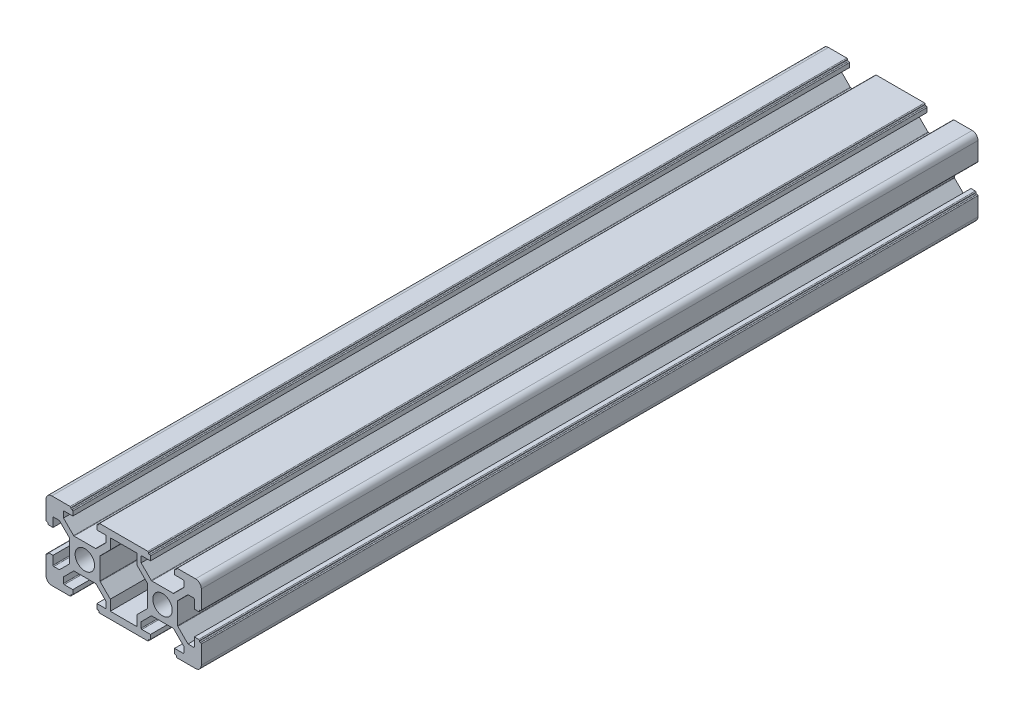
SolidWorks part; units mm, degrees
ref_plane "前视基准面" through (0, 0, 0) normal (0, 0, 1) x (1, 0, 0)
ref_plane "上视基准面" through (0, 0, 0) normal (0, 1, 0) x (1, 0, 0)
ref_plane "右视基准面" through (0, 0, 0) normal (1, 0, 0) x (0, 0, -1)
sketch "Sketch1" plane through (0, 0, 0) normal (0, 0, 1) x (1, 0, 0)
  line L0 (-8.5, 10) -> (-3.8, 10)
  line L3 (-8.5, -10) -> (-3.8, -10)
  line L5 (-10, 8.5) -> (-10, 3.8)
  line L6 (-2.7565, 3.9) -> (2.7565, 3.9)
  line L9 (-2.7565, -3.9) -> (2.7565, -3.9)
  line L10 (3.9, 2.7565) -> (3.9, -2.7565)
  line L11 (-3.9, 2.7565) -> (-3.9, -2.7565)
  line L12 (-3.9586, -2.8979) -> (-6.5607, -5.5)
  line L13 (3.6, 9.7) -> (3.6, 9.8)
  line L14 (3.1, -8.2) -> (5.3, -8.2)
  line L15 (-2.8979, -3.9586) -> (-5.5, -6.5607)
  line L16 (-3.1, -8.2) -> (-3.1, -9.3)
  line L17 (3.1, -8.2) -> (3.1, -9.3)
  line L18 (-5.5, -6.5607) -> (-5.5, -8)
  line L19 (5.5, -6.5607) -> (5.5, -8)
  line L20 (-5.3, -8.2) -> (-3.1, -8.2)
  line L21 (-3.4, -9.5) -> (-3.3, -9.5)
  line L22 (3.8, -10) -> (8.5, -10)
  line L23 (3.3, -9.5) -> (3.4, -9.5)
  line L24 (-3.6, -9.7) -> (-3.6, -9.8)
  line L25 (3.6, -9.7) -> (3.6, -9.8)
  line L26 (-6.5607, -5.5) -> (-8, -5.5)
  line L27 (-9.7, -3.6) -> (-9.8, -3.6)
  line L28 (-9.5, -3.4) -> (-9.5, -3.3)
  line L29 (-8.2, -3.1) -> (-9.3, -3.1)
  line L30 (-8.2, -5.3) -> (-8.2, -3.1)
  line L31 (-10, -3.8) -> (-10, -8.5)
  line L33 (3.8, 10) -> (8.5, 10)
  line L34 (2.8979, -3.9586) -> (5.5, -6.5607)
  line L40 (3.9586, -2.8979) -> (6.5607, -5.5)
  line L41 (3.3, 9.5) -> (3.4, 9.5)
  line L42 (30, 8.5) -> (30, 3.8)
  line L43 (3.1, 8.2) -> (3.1, 9.3)
  line L44 (3.1, 8.2) -> (5.3, 8.2)
  line L45 (5.5, 6.5607) -> (5.5, 8)
  line L46 (2.8979, 3.9586) -> (5.5, 6.5607)
  line L52 (3.9586, 2.8979) -> (6.5607, 5.5)
  line L53 (-3.6, 9.7) -> (-3.6, 9.8)
  line L54 (-3.4, 9.5) -> (-3.3, 9.5)
  line L55 (-3.1, 8.2) -> (-3.1, 9.3)
  line L56 (-5.3, 8.2) -> (-3.1, 8.2)
  line L57 (-5.5, 6.5607) -> (-5.5, 8)
  line L58 (-2.8979, 3.9586) -> (-5.5, 6.5607)
  line L59 (-9.5, 3.4) -> (-9.5, 3.3)
  line L60 (-9.7, 3.6) -> (-9.8, 3.6)
  line L61 (-8.2, 3.1) -> (-9.3, 3.1)
  line L62 (-8.2, 5.3) -> (-8.2, 3.1)
  line L63 (-6.5607, 5.5) -> (-8, 5.5)
  line L64 (-3.9586, 2.8979) -> (-6.5607, 5.5)
  line L65 (29.7, 3.6) -> (29.8, 3.6)
  line L66 (29.5, 3.4) -> (29.5, 3.3)
  line L67 (28.2, 3.1) -> (29.3, 3.1)
  line L68 (28.2, 5.3) -> (28.2, 3.1)
  line L69 (26.5607, 5.5) -> (28, 5.5)
  line L70 (23.9586, 2.8979) -> (26.5607, 5.5)
  line L71 (23.9, 2.7565) -> (23.9, -2.7565)
  line L72 (23.9586, -2.8979) -> (26.5607, -5.5)
  line L73 (26.5607, -5.5) -> (28, -5.5)
  line L74 (28.2, -5.3) -> (28.2, -3.1)
  line L75 (28.2, -3.1) -> (29.3, -3.1)
  line L76 (29.5, -3.4) -> (29.5, -3.3)
  line L77 (29.7, -3.6) -> (29.8, -3.6)
  line L78 (30, -3.8) -> (30, -8.5)
  line L79 (28.5, -10) -> (23.8, -10)
  line L80 (23.6, -9.7) -> (23.6, -9.8)
  line L81 (23.4, -9.5) -> (23.3, -9.5)
  line L82 (23.1, -8.2) -> (23.1, -9.3)
  line L83 (25.3, -8.2) -> (23.1, -8.2)
  line L84 (25.5, -6.5607) -> (25.5, -8)
  line L85 (22.8979, -3.9586) -> (25.5, -6.5607)
  line L86 (22.7565, -3.9) -> (17.2435, -3.9)
  line L87 (17.1021, -3.9586) -> (14.5, -6.5607)
  line L88 (14.5, -6.5607) -> (14.5, -8)
  line L89 (16.9, -8.2) -> (14.7, -8.2)
  line L90 (16.9, -8.2) -> (16.9, -9.3)
  line L91 (16.7, -9.5) -> (16.6, -9.5)
  line L92 (16.4, -9.7) -> (16.4, -9.8)
  line L93 (16.2, -10) -> (11.5, -10)
  line L94 (13.4393, 5.5) -> (13.4393, 8.2)
  line L96 (6.5607, 5.5) -> (6.5607, 8.2)
  line L97 (6.5607, 8.2) -> (13.4393, 8.2)
  line L99 (16.0414, -2.8979) -> (13.4393, -5.5)
  line L100 (16.1, 2.7565) -> (16.1, -2.7565)
  line L101 (16.0414, 2.8979) -> (13.4393, 5.5)
  line L107 (16.2, 10) -> (11.5, 10)
  line L108 (16.4, 9.7) -> (16.4, 9.8)
  line L109 (16.7, 9.5) -> (16.6, 9.5)
  line L110 (16.9, 8.2) -> (16.9, 9.3)
  line L111 (16.9, 8.2) -> (14.7, 8.2)
  line L112 (14.5, 6.5607) -> (14.5, 8)
  line L113 (17.1021, 3.9586) -> (14.5, 6.5607)
  line L114 (22.7565, 3.9) -> (17.2435, 3.9)
  line L115 (22.8979, 3.9586) -> (25.5, 6.5607)
  line L116 (25.5, 6.5607) -> (25.5, 8)
  line L117 (25.3, 8.2) -> (23.1, 8.2)
  line L118 (23.1, 8.2) -> (23.1, 9.3)
  line L119 (23.4, 9.5) -> (23.3, 9.5)
  line L120 (23.6, 9.7) -> (23.6, 9.8)
  line L121 (28.5, 10) -> (23.8, 10)
  line L122 (13.4393, -5.5) -> (13.4393, -8.2)
  line L124 (6.5607, -5.5) -> (6.5607, -8.2)
  line L125 (6.5607, -8.2) -> (13.4393, -8.2)
  line L127 (8.5, 10) -> (11.5, 10)
  line L128 (8.5, -10) -> (11.5, -10)
  arc A3 (-8.5, -10) -> (-10, -8.5) centre (-8.5, -8.5) cw
  arc A4 (-10, 8.5) -> (-8.5, 10) centre (-8.5, 8.5) cw
  arc A5 (3.4, -9.5) -> (3.6, -9.7) centre (3.4, -9.7) cw
  arc A6 (3.8, -10) -> (3.6, -9.8) centre (3.8, -9.8) cw
  arc A7 (3.3, -9.5) -> (3.1, -9.3) centre (3.3, -9.3) cw
  arc A8 (5.3, -8.2) -> (5.5, -8) centre (5.3, -8) ccw
  arc A9 (-3.9, -2.7565) -> (-3.9586, -2.8979) centre (-4.1, -2.7565) cw
  arc A10 (-3.9, 2.7565) -> (-3.9586, 2.8979) centre (-4.1, 2.7565) ccw
  arc A11 (-2.7565, 3.9) -> (-2.8979, 3.9586) centre (-2.7565, 4.1) cw
  arc A12 (2.7565, 3.9) -> (2.8979, 3.9586) centre (2.7565, 4.1) ccw
  arc A13 (3.9586, 2.8979) -> (3.9, 2.7565) centre (4.1, 2.7565) ccw
  arc A14 (3.9, -2.7565) -> (3.9586, -2.8979) centre (4.1, -2.7565) ccw
  arc A15 (-2.8979, -3.9586) -> (-2.7565, -3.9) centre (-2.7565, -4.1) cw
  arc A16 (2.7565, -3.9) -> (2.8979, -3.9586) centre (2.7565, -4.1) cw
  arc A17 (-3.6, -9.8) -> (-3.8, -10) centre (-3.8, -9.8) cw
  arc A18 (-3.3, -9.5) -> (-3.1, -9.3) centre (-3.3, -9.3) ccw
  arc A19 (-3.6, -9.7) -> (-3.4, -9.5) centre (-3.4, -9.7) cw
  arc A20 (-8.2, 5.3) -> (-8, 5.5) centre (-8, 5.3) cw
  arc A23 (-8.2, -5.3) -> (-8, -5.5) centre (-8, -5.3) ccw
  arc A24 (-5.3, -8.2) -> (-5.5, -8) centre (-5.3, -8) cw
  arc A31 (3.1, 9.3) -> (3.3, 9.5) centre (3.3, 9.3) cw
  arc A32 (3.6, 9.8) -> (3.8, 10) centre (3.8, 9.8) cw
  arc A33 (3.6, 9.7) -> (3.4, 9.5) centre (3.4, 9.7) cw
  arc A34 (-3.8, 10) -> (-3.6, 9.8) centre (-3.8, 9.8) cw
  arc A35 (-3.3, 9.5) -> (-3.1, 9.3) centre (-3.3, 9.3) cw
  arc A36 (-3.4, 9.5) -> (-3.6, 9.7) centre (-3.4, 9.7) cw
  arc A37 (5.5, 8) -> (5.3, 8.2) centre (5.3, 8) ccw
  arc A38 (-5.5, 8) -> (-5.3, 8.2) centre (-5.3, 8) cw
  arc A39 (-10, 3.8) -> (-9.8, 3.6) centre (-9.8, 3.8) ccw
  arc A40 (-9.5, 3.3) -> (-9.3, 3.1) centre (-9.3, 3.3) ccw
  arc A41 (-9.7, 3.6) -> (-9.5, 3.4) centre (-9.7, 3.4) cw
  arc A42 (-10, -3.8) -> (-9.8, -3.6) centre (-9.8, -3.8) cw
  arc A43 (-9.5, -3.3) -> (-9.3, -3.1) centre (-9.3, -3.3) cw
  arc A44 (-9.5, -3.4) -> (-9.7, -3.6) centre (-9.7, -3.4) cw
  arc A45 (30, 8.5) -> (28.5, 10) centre (28.5, 8.5) ccw
  arc A46 (30, 3.8) -> (29.8, 3.6) centre (29.8, 3.8) cw
  arc A47 (29.7, 3.6) -> (29.5, 3.4) centre (29.7, 3.4) ccw
  arc A48 (29.5, 3.3) -> (29.3, 3.1) centre (29.3, 3.3) cw
  arc A49 (28.2, 5.3) -> (28, 5.5) centre (28, 5.3) ccw
  arc A50 (23.9, 2.7565) -> (23.9586, 2.8979) centre (24.1, 2.7565) cw
  arc A51 (23.9, -2.7565) -> (23.9586, -2.8979) centre (24.1, -2.7565) ccw
  arc A52 (28.2, -5.3) -> (28, -5.5) centre (28, -5.3) cw
  arc A53 (29.5, -3.3) -> (29.3, -3.1) centre (29.3, -3.3) ccw
  arc A54 (29.5, -3.4) -> (29.7, -3.6) centre (29.7, -3.4) ccw
  arc A55 (30, -3.8) -> (29.8, -3.6) centre (29.8, -3.8) ccw
  arc A56 (28.5, -10) -> (30, -8.5) centre (28.5, -8.5) ccw
  arc A57 (23.6, -9.8) -> (23.8, -10) centre (23.8, -9.8) ccw
  arc A58 (23.6, -9.7) -> (23.4, -9.5) centre (23.4, -9.7) ccw
  arc A59 (23.3, -9.5) -> (23.1, -9.3) centre (23.3, -9.3) cw
  arc A60 (25.3, -8.2) -> (25.5, -8) centre (25.3, -8) ccw
  arc A61 (22.8979, -3.9586) -> (22.7565, -3.9) centre (22.7565, -4.1) ccw
  arc A62 (17.2435, -3.9) -> (17.1021, -3.9586) centre (17.2435, -4.1) ccw
  arc A63 (14.7, -8.2) -> (14.5, -8) centre (14.7, -8) cw
  arc A64 (16.7, -9.5) -> (16.9, -9.3) centre (16.7, -9.3) ccw
  arc A65 (16.6, -9.5) -> (16.4, -9.7) centre (16.6, -9.7) ccw
  arc A66 (16.2, -10) -> (16.4, -9.8) centre (16.2, -9.8) ccw
  arc A72 (16.1, -2.7565) -> (16.0414, -2.8979) centre (15.9, -2.7565) cw
  arc A73 (16.0414, 2.8979) -> (16.1, 2.7565) centre (15.9, 2.7565) cw
  arc A79 (16.4, 9.8) -> (16.2, 10) centre (16.2, 9.8) ccw
  arc A80 (16.4, 9.7) -> (16.6, 9.5) centre (16.6, 9.7) ccw
  arc A81 (16.9, 9.3) -> (16.7, 9.5) centre (16.7, 9.3) ccw
  arc A82 (14.5, 8) -> (14.7, 8.2) centre (14.7, 8) cw
  arc A83 (17.2435, 3.9) -> (17.1021, 3.9586) centre (17.2435, 4.1) cw
  arc A84 (22.7565, 3.9) -> (22.8979, 3.9586) centre (22.7565, 4.1) ccw
  arc A85 (25.5, 8) -> (25.3, 8.2) centre (25.3, 8) ccw
  arc A86 (23.3, 9.5) -> (23.1, 9.3) centre (23.3, 9.3) ccw
  arc A87 (23.4, 9.5) -> (23.6, 9.7) centre (23.4, 9.7) ccw
  arc A88 (23.8, 10) -> (23.6, 9.8) centre (23.8, 9.8) ccw
  point P11 (3.9, 3.9)
  point P19 (3.3697, 4.4303)
  point P20 (-10.6428, -10.6428)
  point P25 (-11.1731, -10.1124)
  point P26 (4.4303, 3.3697)
  point P28 (-10.1124, -11.1731)
  dimension "D3" = 0.2
  dimension "D4" = 0.2
  dimension "D5" = 0.2
  dimension "D8" = 0.2
  dimension "D9" = 0.2
  dimension "D10" = 0.2
  dimension "D6" = 1.8
  dimension "D7" = 0.5
extrude "Boss-Extrude1" add sketch "Sketch1" along normal blind 200
ref_plane "hole" through (0, 0, 200) normal (0, 0, 1) x (1, 0, 0)
sketch "Sketch2" plane through (0, 0, 200) normal (0, 0, 1) x (1, 0, 0)
  circle A0 centre (0, 0) radius 2.5
  circle A1 centre (20, 0) radius 2.5
  dimension "D1" = 5
extrude "Cut-Extrude1" cut sketch "Sketch2" against normal through all
